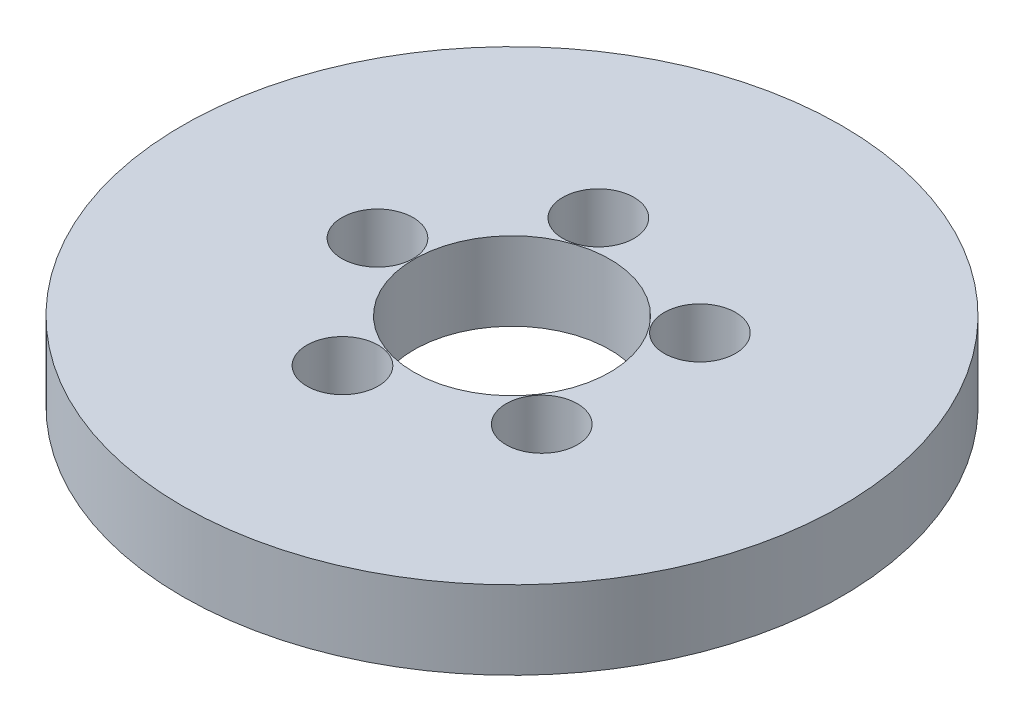
SolidWorks part; units mm, degrees
ref_plane "Front Plane" through (0, 0, 0) normal (0, 0, 1) x (1, 0, 0)
ref_plane "Top Plane" through (0, 0, 0) normal (0, 1, 0) x (1, 0, 0)
ref_plane "Right Plane" through (0, 0, 0) normal (1, 0, 0) x (0, 0, -1)
sketch "Sketch1" plane through (0, 0, 0) normal (0, 1, 0) x (1, 0, 0)
  circle A0 centre (0, 0) radius 92.5
  dimension "FLANGE_OD" = 185
extrude "Boss-Extrude1" add sketch "Sketch1" along normal blind 22
sketch "Sketch2" plane through (0, 0, 0) normal (0, 1, 0) x (1, 0, 0)
  circle A0 centre (0, 0) radius 27.5
  dimension "BORE_D" = 55
extrude "Cut-Extrude1" cut sketch "Sketch2" along normal through all
sketch "Sketch3" plane through (0, 22, 0) normal (0, 1, 0) x (1, 0, 0)
  circle A0 centre (0, 0) radius 37.756 construction
  circle A1 centre (-37.756, 0) radius 10
  dimension "BOLT_D" = 20
  dimension "BOLT_PCD" = 75.5121
extrude "Cut-Extrude2" cut sketch "Sketch3" against normal blind 16.8837
pattern_circular "CirPattern1" count 5 over 360 about axis through (0, 0, 0) along (0, 1, 0) of "Cut-Extrude2"
